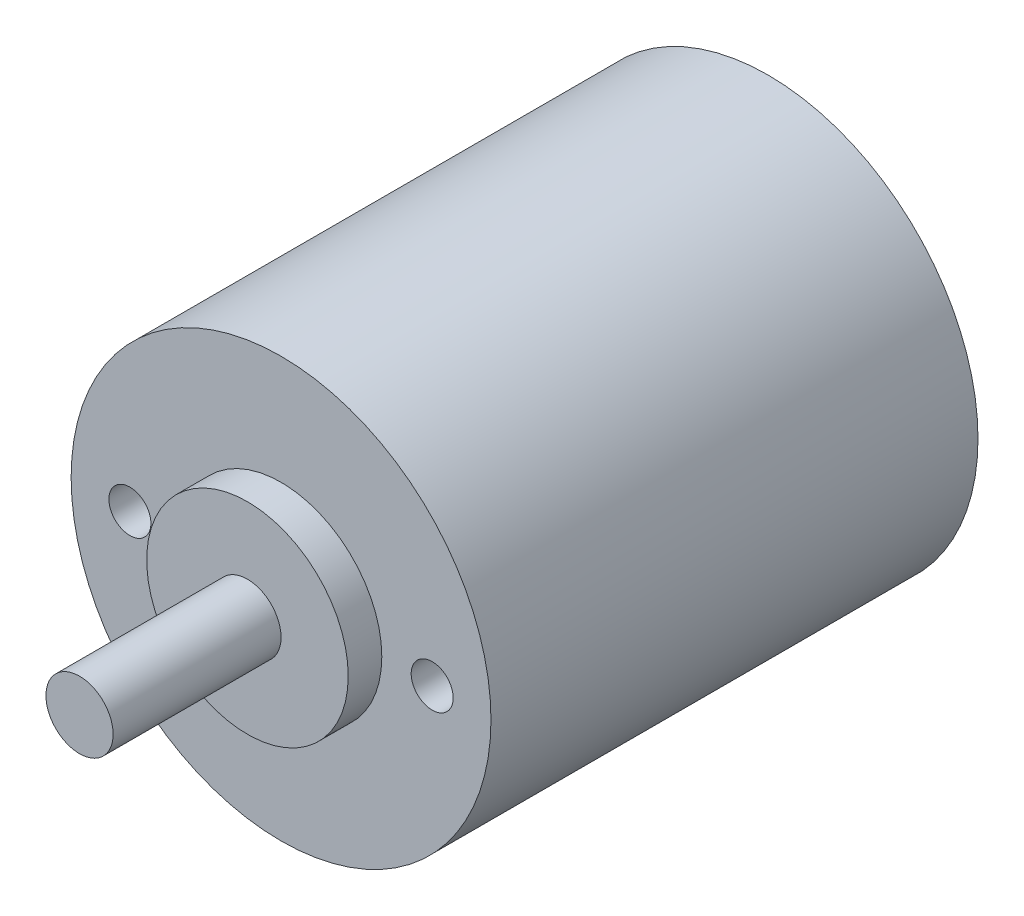
SolidWorks part; units mm, degrees
ref_plane "Front Plane" through (0, 0, 0) normal (0, 0, 1) x (1, 0, 0)
ref_plane "Top Plane" through (0, 0, 0) normal (0, 1, 0) x (1, 0, 0)
ref_plane "Right Plane" through (0, 0, 0) normal (1, 0, 0) x (0, 0, -1)
sketch "Sketch1" plane through (0, 0, 0) normal (0, 0, 1) x (1, 0, 0)
  circle A0 centre (0, 0) radius 12.5
  dimension "D1" = 25
extrude "Boss-Extrude1" add sketch "Sketch1" along normal blind 29
sketch "Sketch2" plane through (0, 0, 29) normal (0, 0, 1) x (1, 0, 0)
  circle A0 centre (0, 0) radius 2
  dimension "D1" = 4
extrude "Boss-Extrude2" add sketch "Sketch2" along normal blind 12
sketch "Sketch3" plane through (0, 0, 29) normal (0, 0, 1) x (1, 0, 0)
  circle A0 centre (0, 0) radius 6
  dimension "D1" = 12
extrude "Boss-Extrude3" add sketch "Sketch3" along normal blind 2
hole_wizard "M3x0.5 Tapped Hole1" positions "Sketch5" profile "Sketch4" tap size "M3x0.5" standard "Ansi Metric"
sketch "Sketch5" plane through (0, 0, 29) normal (0, 0, 1) x (1, 0, 0)
  line L0 (-9, 0) -> (9, 0)
  circle A0 centre (0, 0) radius 9
  point P0 (-9, 0)
  point P1 (9, 0)
  dimension "D1" = 18
sketch "Sketch4" plane through (-9, 0, 29) normal (1, 0, 0) x (0, -1, 0)
  line L0 (0, 0) -> (0, 4.7511)
  line L1 (0, 4.7511) -> (1.25, 4)
  line L2 (1.25, 4) -> (1.25, 0)
  line L5 (1.25, 0) -> (0, 0)
  line L10 (0, 4.7511) -> (-1.25, 4) construction
  line L11 (0, -6.35) -> (0, 107.95) construction
  dimension "Tap Drill Dia." = 2.5
  dimension "Tap Drill Depth" = 4
  dimension "Drill Angle" = 118
